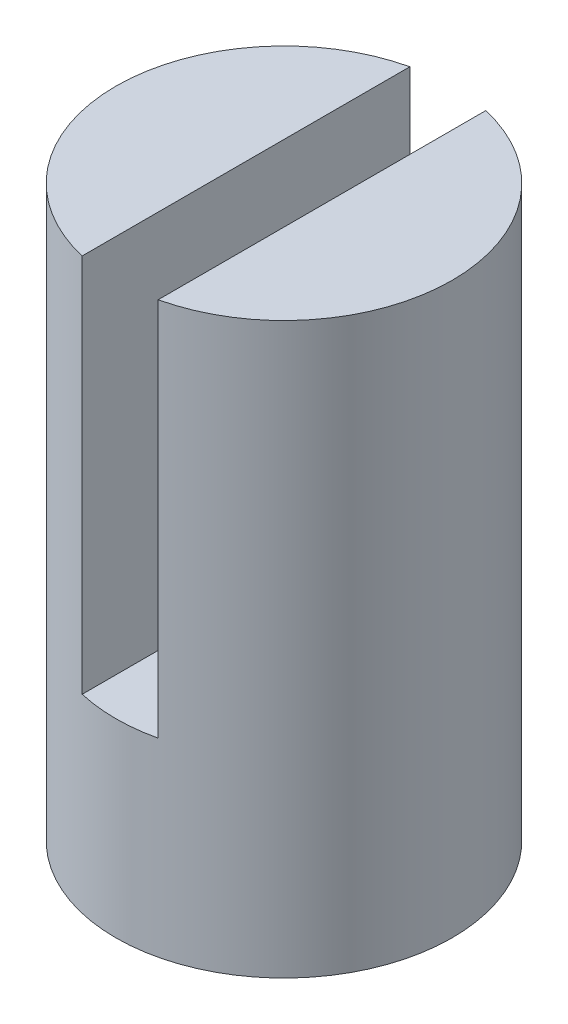
SolidWorks part; units mm, degrees
ref_plane "Front Plane" through (0, 0, 0) normal (0, 0, 1) x (1, 0, 0)
ref_plane "Top Plane" through (0, 0, 0) normal (0, 1, 0) x (1, 0, 0)
ref_plane "Right Plane" through (0, 0, 0) normal (1, 0, 0) x (0, 0, -1)
sketch "Sketch1" plane through (0, 0, 0) normal (0, 1, 0) x (1, 0, 0)
  line L1 (-1.27, -5.6261) -> (1.27, -5.6261)
  line L2 (-1.27, -5.6261) -> (-1.27, 5.6261)
  line L3 (-1.27, 5.6261) -> (1.27, 5.6261)
  line L4 (1.27, -5.6261) -> (1.27, 5.6261)
  line L5 (-1.27, -5.6261) -> (1.27, 5.6261) construction
  line L6 (-1.27, 5.6261) -> (1.27, -5.6261) construction
  circle A0 centre (0, 0) radius 5.6261
  dimension "D1" = 11.2522
  dimension "D2" = 2.54
extrude "Boss-Extrude1" add sketch "Sketch1" along normal blind 6.35 contours L2 A0 | L4 A0 L2 | L4 A0 region at (0, 0, 0) region at (-3.0874, 0, 0) region at (3.0874, 0, 0)
extrude "Boss-Extrude2" add sketch "Sketch1<3>" along normal blind 12.7 from surface contours L2 A0 | L4 A0 region at (-3.0874, 0, 0) region at (3.0874, 0, 0) starting at face at (0, 6.35, 5.6261)
sketch "Sketch1<3>" plane through (0, 0, 0) normal (0, 1, 0) x (1, 0, 0) same geometry as "Sketch1"
